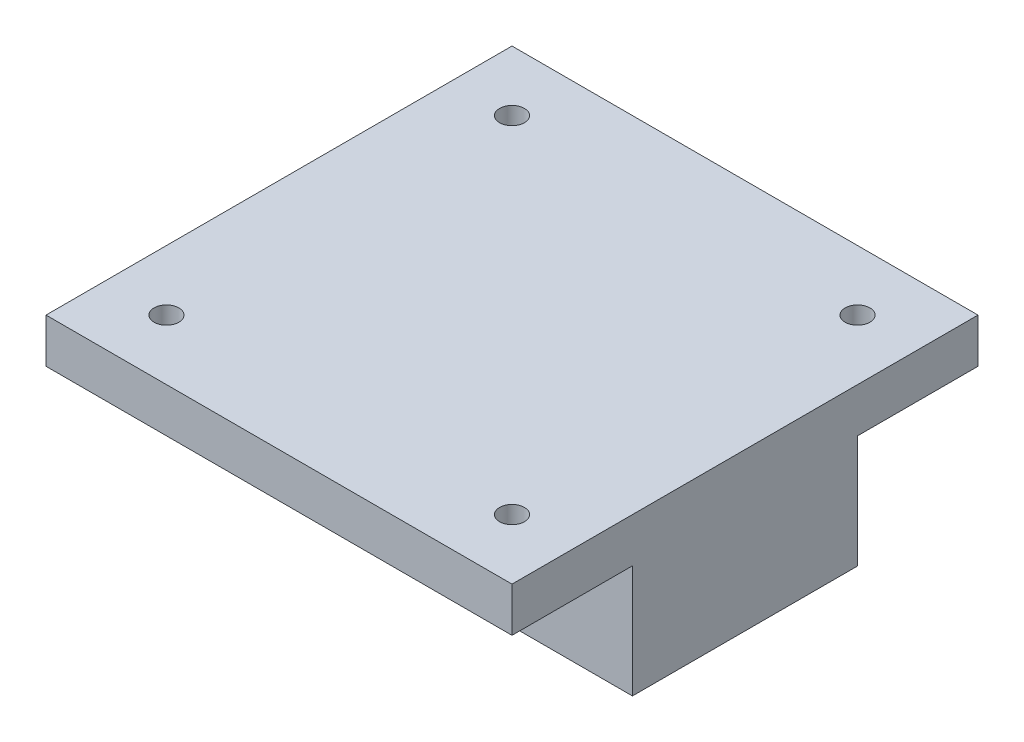
SolidWorks part; units mm, degrees
material "PETG"
ref_plane "Front Plane" through (0, 0, 0) normal (0, 0, 1) x (1, 0, 0)
ref_plane "Top Plane" through (0, 0, 0) normal (0, 1, 0) x (1, 0, 0)
ref_plane "Right Plane" through (0, 0, 0) normal (1, 0, 0) x (0, 0, -1)
sketch "Sketch1" plane through (0, 0, 0) normal (0, 1, 0) x (1, 0, 0)
  line L0 (-38.9313, 38.9312) -> (-38.9313, 52.5) construction
  line L1 (-52.5, -25.3625) -> (52.5, -25.3625)
  line L2 (-52.5, -25.3625) -> (-52.5, 25.3625)
  line L3 (-52.5, 25.3625) -> (52.5, 25.3625)
  line L4 (52.5, -25.3625) -> (52.5, 25.3625)
  line L5 (-52.5, 52.5) -> (52.5, 52.5)
  line L6 (-52.5, 52.5) -> (-52.5, -52.5)
  line L7 (-52.5, -52.5) -> (52.5, -52.5)
  line L8 (52.5, 52.5) -> (52.5, -52.5)
  line L9 (-38.9313, 38.9312) -> (-52.5, 38.9312) construction
  line L10 (-38.9313, 38.9312) -> (-38.9313, 25.3625) construction
  line L11 (38.9313, 38.9312) -> (52.5, 38.9312) construction
  line L13 (-38.9313, -38.9312) -> (-38.9313, -25.3625) construction
  circle A0 centre (-38.9313, 38.9312) radius 2.8
  circle A1 centre (38.9313, 38.9312) radius 2.8
  circle A2 centre (-38.9313, -38.9312) radius 2.8
  circle A3 centre (38.9313, -38.9312) radius 2.8
  point P4 (-52.5, 0)
  point P5 (0, 25.3625)
  dimension "D4" = 5.6
  dimension "D1" = 50.725
  dimension "D2" = 105
  dimension "D3" = 105
extrude "Boss-Extrude1" add sketch "Sketch1" along normal blind 10 contours L1 L4 L3 L2 | L8 L1 L6 L7 | L8 L5 L6 L3 region at (0, 0, 0) region at (0, 0, 38.9313) region at (0, 0, -38.9312)
extrude "Boss-Extrude2" add sketch "Sketch1<3>" against normal blind 25.4 contours L1 L4 L3 L2 region at (0, 0, 0)
sketch "Sketch1<3>" plane through (0, 0, 0) normal (0, 1, 0) x (1, 0, 0) same geometry as "Sketch1"
equation "\"tol_dia_id_intfc\" = 0.0500mm ' For hole diameters - Interference fit"
equation "\"tol_dia_id_slip\"  = 0.0750mm ' For hole diameters - Slip fit"
equation "\"tol_dia_id_clear\" = 0.1000mm ' For hole diameters - Clearance fit"
equation "\"tol_dia_od_intfc\" = 0.0500mm ' For shaft diameters - Interference fit"
equation "\"tol_dia_od_slip\"  = 0.0750mm ' For shaft diameters - Slip fit"
equation "\"tol_dia_od_clear\" = 0.1000mm ' For shaft diameters - Clearance fit"
equation "\"tol_general_intfc\"= 0.0250mm ' For general parts (Horiz) - Interference fit"
equation "\"tol_general_slip\" = 0.0375mm ' For general parts (Horiz) - Slip fit"
equation "\"tol_general_clear\"= 0.0500mm ' For general parts (Horiz) - Clearance fit"
equation "\"tol_layer_intfc\"  = 0.0250mm ' For all parts (Vert) - Interference fit"
equation "\"tol_layer_slip\"   = 0.0375mm ' For all parts (Vert) - Slip fit"
equation "\"tol_layer_clear\"  = 0.0500mm ' For all parts (Vert) - Clearance fit"
equation "\"tol_corner_rad\"   = 0.100mm ' For corners that fit into other parts"
equation "\"D1@Sketch1\"=50.80mm-\"tol_general_slip\"*2"
